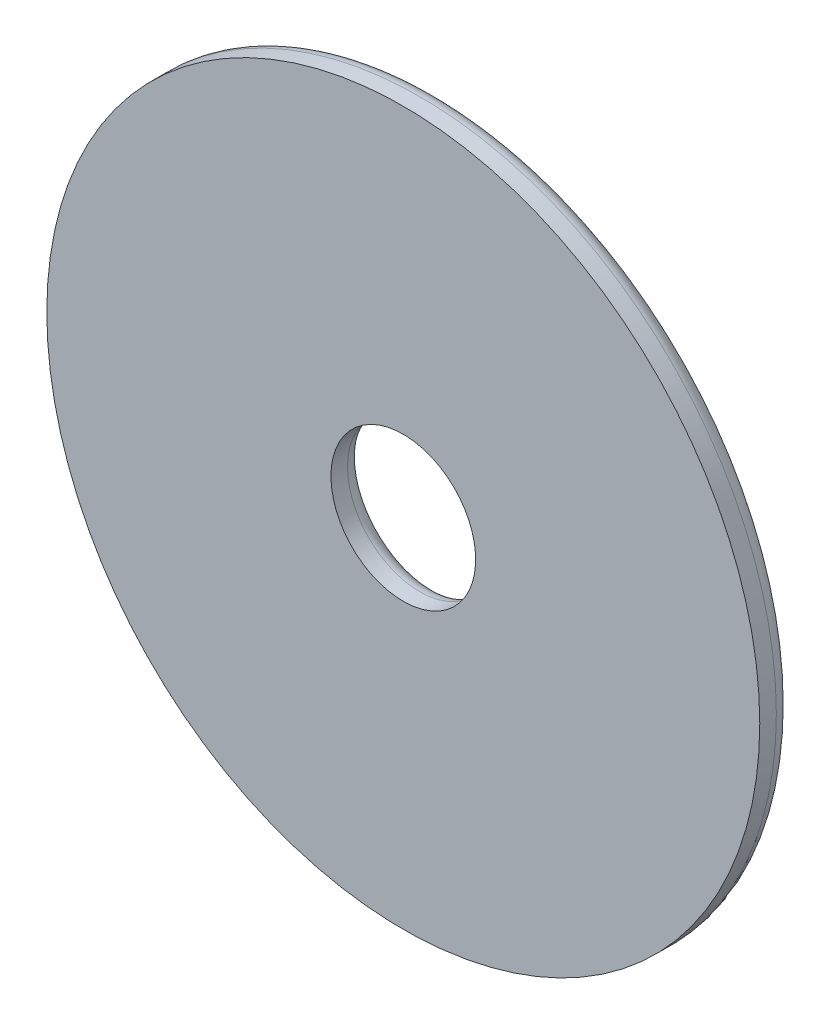
SolidWorks part; units mm, degrees
ref_plane "Front Plane" through (0, 0, 0) normal (0, 0, 1) x (1, 0, 0)
ref_plane "Top Plane" through (0, 0, 0) normal (0, 1, 0) x (1, 0, 0)
ref_plane "Right Plane" through (0, 0, 0) normal (1, 0, 0) x (0, 0, -1)
sketch "Sketch1" plane through (0, 0, 0) normal (0, 0, 1) x (1, 0, 0)
  line L0 (-12.7, 0) -> (12.7, 0) construction
  line L1 (0, 12.7) -> (0, -12.7) construction
  circle A0 centre (0, 0) radius 12.7 construction
  circle A1 centre (0, 0) radius 2.5781 construction
  point P4 (0, 0)
  point P8 (0, -2.5781)
  point P9 (2.5781, 0)
  point P10 (0, 2.5781)
  point P11 (-2.5781, 0)
  dimension "OD" = 25.4
  dimension "ID" = 5.1562
sketch "Sketch2" plane through (0, 0, 0) normal (1, 0, 0) x (0, 0, -1)
  line L0 (0.5906, 0) -> (-0.5906, 0) construction
  line L1 (0.5905, 12.7) -> (-0.5906, 12.7) construction
  line L2 (0.5905, 12.7) -> (0.5905, -12.7) construction
  line L3 (0.5905, -12.7) -> (-0.5906, -12.7) construction
  line L4 (-0.5906, 12.7) -> (-0.5906, -12.7) construction
  line L5 (-0.5906, 2.5781) -> (0.5905, 2.5781) construction
  line L6 (-0.5906, -2.5781) -> (0.5905, -2.5781) construction
  line L7 (-0.6477, 0) -> (0.6477, 0) construction
  line L8 (0, 12.7) -> (0, -12.7) construction
  point P6 (0, 0)
  point P17 (0, 0)
  point P18 (-0.5334, 0)
  point P21 (0.5334, 0)
  dimension "Thickness" = 1.1811
  dimension "Max Thickness Range" = 1.2954
  dimension "Min Thickness Range" = 1.0668
sketch "Sketch3" plane through (0, 0, 0) normal (0, 0, 1) x (1, 0, 0)
  line L0 (-12.7, 0) -> (12.7, 0) construction
  circle A0 centre (0, 0) radius 12.7
  circle A1 centre (0, 0) radius 2.5781
  circle A2 centre (0, 0) radius 12.7 construction
  circle A3 centre (0, 0) radius 2.5781 construction
extrude "Boss-Extrude1" add sketch "Sketch3" along normal up to vertex (0.5906 mm away) and the other way up to vertex (0.5906 mm away) up to point (0, 0, 0.5906) other way up to point (0, 0, -0.5906)
fillet "Fillet1" radius 0.5906 2 edges at (12.7, 0, -0.5906) (2.5781, 0, -0.5906)
equation "\"D1@Fillet1\"=\"Thickness@Sketch2\"*.5"
